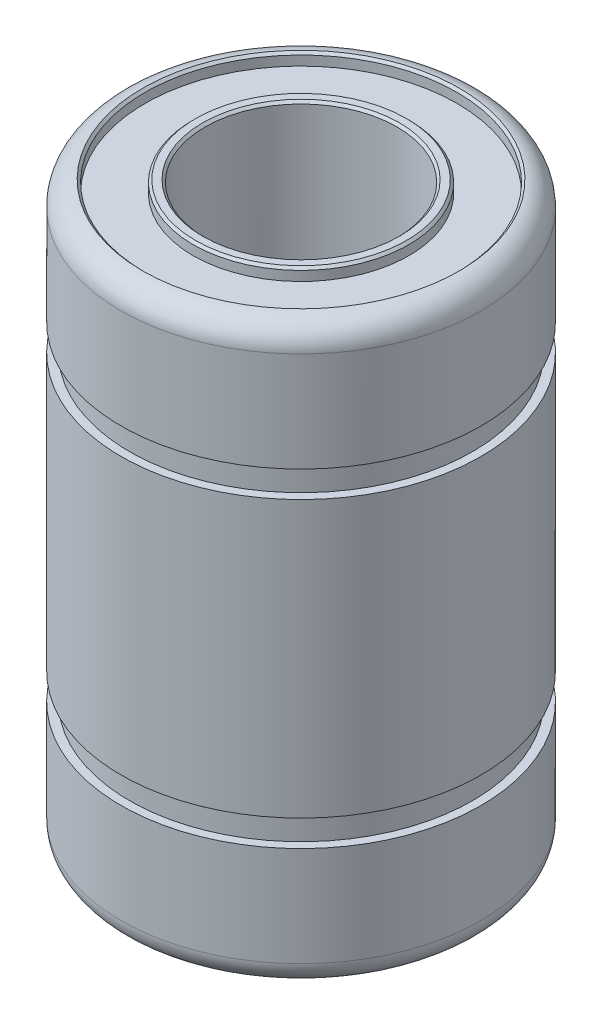
SolidWorks part; units mm, degrees
ref_plane "Front Plane" through (0, 0, 0) normal (0, 0, 1) x (1, 0, 0)
ref_plane "Top Plane" through (0, 0, 0) normal (0, 1, 0) x (1, 0, 0)
ref_plane "Right Plane" through (0, 0, 0) normal (1, 0, 0) x (0, 0, -1)
sketch "Sketch1" plane through (0, 0, 0) normal (0, 0, 1) x (1, 0, 0)
  line L0 (0, 0) -> (0, 22.7522) construction
  line L1 (7.15, 17.75) -> (7.15, 6.25) construction
  line L2 (4, 0) -> (4.5, 0)
  line L3 (4, 0) -> (4, 24)
  line L4 (4, 24) -> (4.5, 24)
  line L5 (7.5, 18.85) -> (7.5, 24)
  line L6 (7.5, 18.85) -> (7.15, 18.85)
  line L7 (6.5, 24) -> (7.5, 24)
  line L8 (7.5, 17.75) -> (7.15, 17.75)
  line L9 (7.15, 18.85) -> (7.15, 17.75)
  line L10 (7.5, 6.25) -> (7.15, 6.25)
  line L11 (7.5, 5.15) -> (7.5, 0)
  line L12 (7.5, 5.15) -> (7.15, 5.15)
  line L13 (7.15, 6.25) -> (7.15, 5.15)
  line L14 (7.15, 12) -> (7.5, 12) construction
  line L15 (7.5, 17.75) -> (7.5, 6.25)
  line L16 (6.5, 0) -> (7.5, 0)
  line L17 (4.5, 24) -> (4.5, 23.5)
  line L18 (4.5, 23.5) -> (6.5, 23.5)
  line L19 (6.5, 24) -> (6.5, 23.5)
  line L21 (6.5, 0) -> (6.5, 0.5)
  line L22 (6.5, 0.5) -> (4.5, 0.5)
  line L23 (4.5, 0) -> (4.5, 0.5)
  dimension "D1" = 8
  dimension "D2" = 15
  dimension "D3" = 24
  dimension "D4" = 1.1
  dimension "D5" = 11.5
  dimension "D6" = 14.3
  dimension "D7" = 12
  dimension "D8" = 0.5
  dimension "D9" = 1
  dimension "D10" = 0.5
revolve "Revolve1" add sketch "Sketch1" angle 360 about L0
chamfer "Chamfer1" distance 0.1 angle 45 6 edges at (0, 0, -6.5) (0, 0, -4.5) (0, 0, -4) (0, 24, -6.5) (0, 24, -4.5) (0, 24, -4)
fillet "Fillet1" radius 1 2 edges at (0, 0, -7.5) (0, 24, -7.5)
